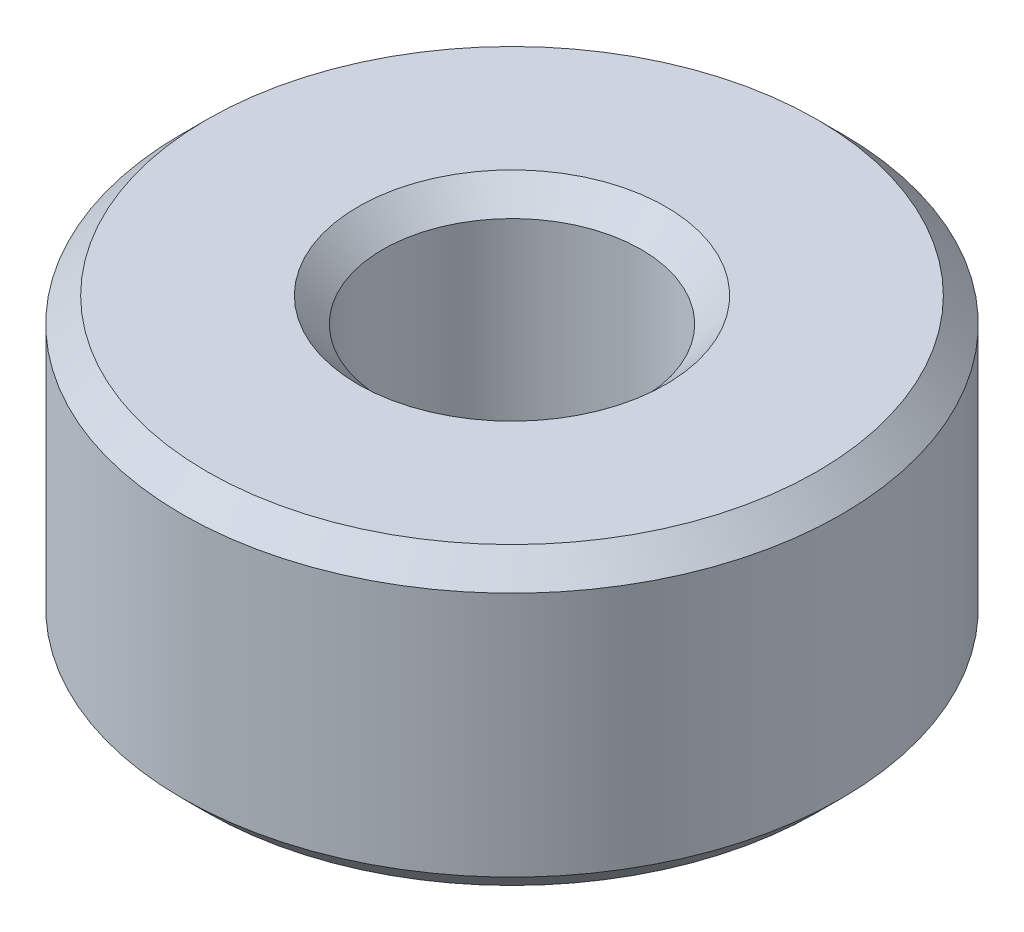
SolidWorks part; units mm, degrees
ref_plane "Front Plane" through (0, 0, 0) normal (0, 0, 1) x (1, 0, 0)
ref_plane "Top Plane" through (0, 0, 0) normal (0, 1, 0) x (1, 0, 0)
ref_plane "Right Plane" through (0, 0, 0) normal (1, 0, 0) x (0, 0, -1)
sketch "Sketch1" plane through (0, 0, 0) normal (0, 1, 0) x (1, 0, 0)
  circle A0 centre (0, 0) radius 7.5
  dimension "SLEEVE_OD" = 15
extrude "Boss-Extrude1" add sketch "Sketch1" along normal blind 6.7164
sketch "Sketch2" plane through (0, 0, 0) normal (0, 1, 0) x (1, 0, 0)
  circle A0 centre (0, 0) radius 2.9394
  dimension "BORE_D" = 5.8788
extrude "Cut-Extrude1" cut sketch "Sketch2" along normal through all
chamfer "Chamfer1" distance 0.5616 angle 45 4 edges at (0, 6.7164, 2.9394) (0, 0, 2.9394) (0, 0, 7.5) (0, 6.7164, 7.5)
